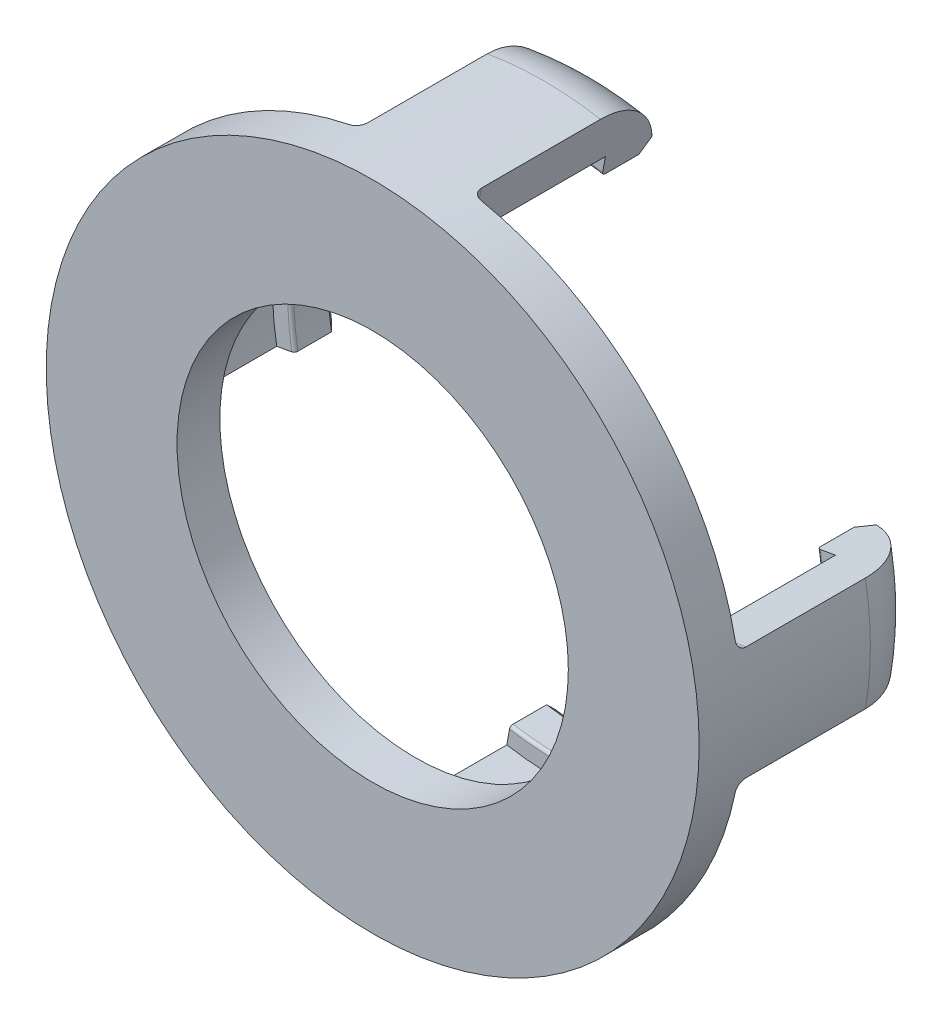
SolidWorks part; units mm, degrees
ref_plane "Front Plane" through (0, 0, 0) normal (0, 0, 1) x (1, 0, 0)
ref_plane "Top Plane" through (0, 0, 0) normal (0, 1, 0) x (1, 0, 0)
ref_plane "Right Plane" through (0, 0, 0) normal (1, 0, 0) x (0, 0, -1)
sketch "Sketch1" plane through (0, 0, 0) normal (0, 0, 1) x (1, 0, 0)
  circle A0 centre (0, 0) radius 16
  circle A1 centre (0, 0) radius 22.7 construction
  circle A2 centre (0, 0) radius 26.7
  dimension "D1" = 32
  dimension "D2" = 45.4
  dimension "D3" = 53.4
extrude "Boss-Extrude1" add sketch "Sketch1" along normal blind 3.5
ref_axis "Axis1" through (0, 0, -0.32) along (0, 0, 1)
sketch "Sketch6" plane through (0, 0, 0) normal (0, 0, 1) x (1, 0, 0)
  circle A0 centre (0, 0) radius 21.7 construction
  circle A1 centre (0, 0) radius 21.7
  circle A2 centre (0, 0) radius 26.7
  dimension "D1" = 43.4
extrude "Boss-Extrude2" add sketch "Sketch6" against normal blind 15.5
ref_plane "Plane2" through (0, 0, -15.5) normal (0, 0, -1) x (-1, 0, 0)
sketch "Sketch8" plane through (0, 0, -15.5) normal (0, 0, -1) x (-1, 0, 0)
  line L0 (-4.6364, -26.2944) -> (-3.7682, -21.3703)
  line L1 (-26.2944, -4.6364) -> (-21.3703, -3.7682)
  line L2 (-26.2944, 4.6364) -> (-21.3703, 3.7682)
  line L3 (-4.6364, 26.2944) -> (-3.7682, 21.3703)
  line L4 (4.6364, 26.2944) -> (3.7682, 21.3703)
  line L5 (26.2944, 4.6364) -> (21.3703, 3.7682)
  line L6 (26.2944, -4.6364) -> (21.3703, -3.7682)
  line L7 (4.6364, -26.2944) -> (3.7682, -21.3703)
  arc A0 (-26.2944, -4.6364) -> (-4.6364, -26.2944) centre (0, 0) ccw
  arc A1 (21.3703, 3.7682) -> (3.7682, 21.3703) centre (0, 0) ccw
  arc A2 (-4.6364, 26.2944) -> (-26.2944, 4.6364) centre (0, 0) ccw
  arc A3 (3.7682, -21.3703) -> (21.3703, -3.7682) centre (0, 0) ccw
  arc A4 (26.2944, 4.6364) -> (4.6364, 26.2944) centre (0, 0) ccw
  arc A5 (-21.3703, -3.7682) -> (-3.7682, -21.3703) centre (0, 0) ccw
  arc A6 (4.6364, -26.2944) -> (26.2944, -4.6364) centre (0, 0) ccw
  arc A8 (-3.7682, 21.3703) -> (-21.3703, 3.7682) centre (0, 0) ccw
  point P20 (0, 0)
  dimension "D1" = 4
extrude "Cut-Extrude2" cut sketch "Sketch8" against normal up to surface (15.5 mm away) up to face at (16, 0, 0)
ref_plane "Plane3" through (0, 0, 0) normal (-0.1736, -0.9848, 0) x (-0.9848, 0.1736, 0)
sketch "Sketch9" plane through (0, 0, 0) normal (-0.1736, -0.9848, 0) x (-0.9848, 0.1736, 0)
  line L0 (-1022.1372, 11.5) -> (48977.8628, 11.5) construction
  line L1 (-21.7, 0) -> (-26.7, 0) construction
  line L3 (-21.7, 0) -> (-23.2, 0)
  line L4 (-21.7, 0) -> (-21.7, 11.5)
  line L5 (-21.7, 11.5) -> (-23.2, 11.5)
  line L6 (-23.2, 0) -> (-23.2, 11.5)
  dimension "D1" = 11.5
  dimension "D2" = 1.5
revolve "Cut-Revolve2" cut sketch "Sketch9" angle 360 about axis through (0, 0, -0.32) along (0, 0, 1)
fillet "Fillet1" radius 0.25 4 edges at (0, -21.7, -11.5) (-21.7, 0, -11.5) (0, 21.7, -11.5) (21.7, 0, -11.5)
fillet "Fillet3" radius 0.75 8 edges at (-4.3325, -24.571, 0) (4.3325, -24.571, 0) (24.571, 4.3325, 0) (-24.571, 4.3325, 0) (-24.571, -4.3325, 0) (-4.3325, 24.571, 0) (4.3325, 24.571, 0) (24.571, -4.3325, 0)
fillet "Fillet4" radius 5 4 edges at (0, -26.7, -15.5) (-26.7, 0, -15.5) (0, 26.7, -15.5) (26.7, 0, -15.5)
chamfer "Chamfer1" distance 1 angle 45 4 edges at (-21.7, 0, -15.5) (0, 21.7, -15.5) (21.7, 0, -15.5) (0, -21.7, -15.5)
